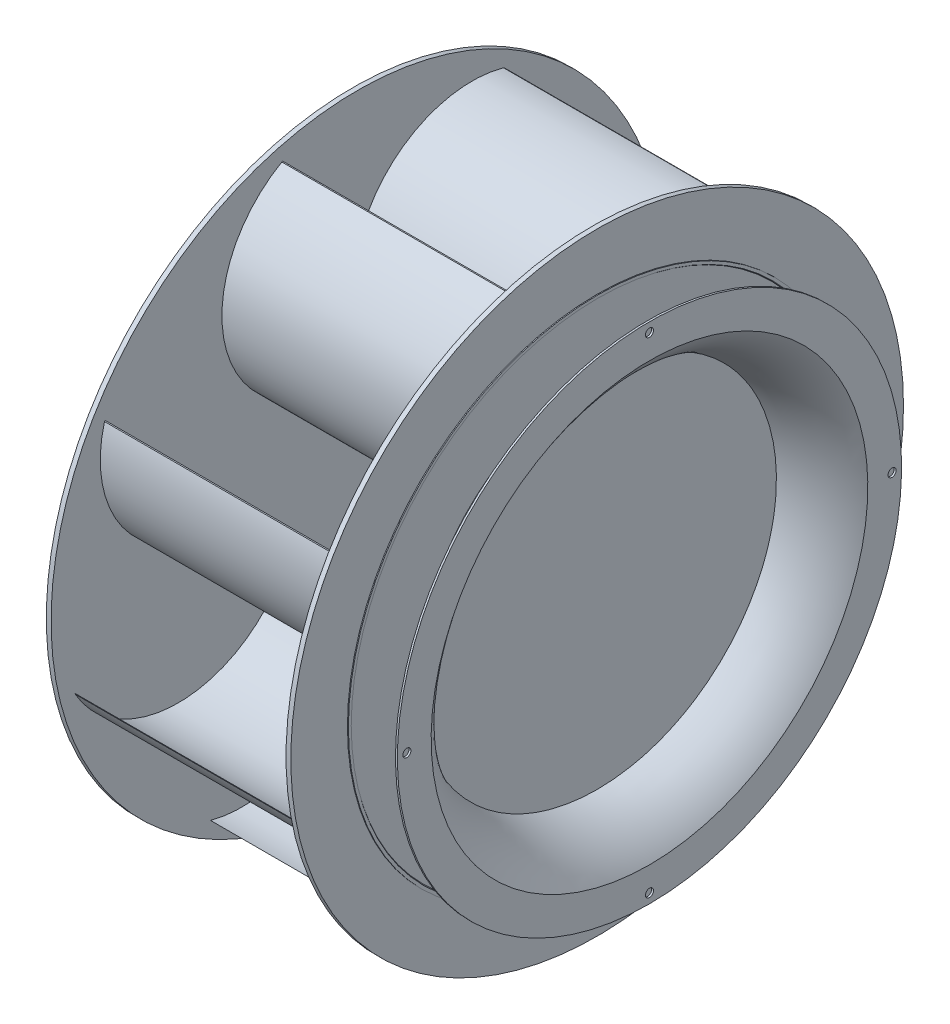
SolidWorks part; units mm, degrees
ref_plane "Front Plane" through (0, 0, 0) normal (0, 0, 1) x (1, 0, 0)
ref_plane "Top Plane" through (0, 0, 0) normal (0, 1, 0) x (1, 0, 0)
ref_plane "Right Plane" through (0, 0, 0) normal (1, 0, 0) x (0, 0, -1)
sketch "Sketch1" plane through (0, 0, 0) normal (0, 0, 1) x (1, 0, 0)
  line L0 (0, 0) -> (831.9083, 0) construction
  line L1 (0, 0) -> (0, 109)
  line L2 (5, 114) -> (70, 114)
  line L3 (70, 114) -> (70, 138)
  line L4 (70, 138) -> (90, 138)
  line L5 (90, 138) -> (90, 98)
  line L6 (90, 98) -> (95, 98)
  line L7 (95, 98) -> (95, 133)
  line L8 (95, 133) -> (105, 133)
  line L9 (105, 133) -> (105, 98)
  line L10 (105, 98) -> (129, 98)
  line L11 (129, 98) -> (129, 0)
  line L12 (129, 0) -> (0, 0)
  arc A0 (5, 114) -> (0, 109) centre (5, 109) ccw
  point P16 (0, 114)
  dimension "D10" = 5
  dimension "D1" = 114
  dimension "D2" = 24
  dimension "D3" = 70
  dimension "D4" = 40
  dimension "D5" = 35
  dimension "D6" = 5
  dimension "D7" = 20
  dimension "D8" = 10
  dimension "D9" = 59
revolve "Revolve1" add sketch "Sketch1" angle 360 about L0
sketch "Sketch2" plane through (129, 0, 0) normal (1, 0, 0) x (0, 0, -1)
  circle A0 centre (0, 0) radius 322
  dimension "D1" = 644
extrude "Extrude1" add sketch "Sketch2" along normal blind 5
sketch "Sketch9" plane through (129, 0, 0) normal (-1, 0, 0) x (0, 0, 1)
  circle A0 centre (0, 0) radius 317
  circle A1 centre (0, 0) radius 100
  circle A2 centre (0, 0) radius 322 construction
  dimension "D1" = 5
  dimension "D2" = 200
extrude "Extrude7" cut sketch "Sketch9" against normal blind 3
ref_plane "Plane1" through (381, 0, 0) normal (1, 0, 0) x (0, 0, -1)
sketch "Sketch3" plane through (381, 0, 0) normal (1, 0, 0) x (0, 0, -1)
  circle A0 centre (0, 0) radius 322
  dimension "D1" = 644
extrude "Extrude2" add sketch "Sketch3" along normal blind 5 separate body
sketch "Sketch4" plane through (134, 0, 0) normal (1, 0, 0) x (0, 0, -1)
  line L0 (0, 0) -> (0, 307) construction
  line L1 (0, 0) -> (161, 278.8602) construction
  line L2 (0, 112.5) -> (0.866, 112)
  line L3 (153.5, 265.8698) -> (154.366, 265.3698)
  circle A0 centre (0, 0) radius 307 construction
  circle A1 centre (0, 0) radius 322 construction
  circle A2 centre (0, 0) radius 112.5 construction
  arc A3 (0, 112.5) -> (153.5, 265.8698) centre (120.6282, 145.2694) cw
  arc A4 (0.866, 112) -> (154.366, 265.3698) centre (121.4942, 144.7694) cw
  dimension "D1" = 15
  dimension "D2" = 225
  dimension "D6" = 125
  dimension "D7" = 125
  dimension "D3" = 30
  dimension "D4" = 60
  dimension "D5" = 1
extrude "Extrude3" add sketch "Sketch4" along normal up to surface (252 mm away) up to face at (386, 0, -322)
ref_axis "Axis1" through (253.5503, 0, 0) along (-1, 0, 0)
pattern_circular "CirPattern1" count 8 over 360 about axis through (253.5503, 0, 0) along (-1, 0, 0) of "Extrude3"
sketch "Sketch5" plane through (0, 0, 0) normal (0, 0, 1) x (1, 0, 0)
  line L0 (0, 0) -> (527.2916, 0) construction
  line L1 (253.5503, 0) -> (75.411, 0) construction
  line L2 (386, 262.5) -> (387, 262.5)
  line L3 (387, 262.5) -> (387, 259.5)
  line L4 (386, 262.5) -> (386, 259.5)
  line L5 (360, 182.5) -> (360, 181.5)
  line L6 (70, 138) -> (70, -138) construction
  line L7 (386, -322) -> (386, 322) construction
  arc A0 (387, 259.5) -> (360, 182.5) centre (427.1772, 202.1781) ccw
  arc A1 (386, 259.5) -> (360, 181.5) centre (426.7494, 202.5835) ccw
  dimension "D7" = 70
  dimension "D8" = 70
  dimension "D1" = 181.5
  dimension "D2" = 1
  dimension "D3" = 1
  dimension "D4" = 3
  dimension "D5" = 262.5
  dimension "D6" = 290
revolve "Revolve2" add sketch "Sketch5" angle 360 about L0
ref_plane "Plane3" through (441, 0, 0) normal (1, 0, 0) x (0, 0, -1)
sketch "Sketch6" plane through (0, 0, 0) normal (0, 0, 1) x (1, 0, 0)
  line L0 (441, 265) -> (439, 265)
  line L1 (441, -251.35) -> (441, 251.35) construction
  line L2 (439, 265) -> (439, 229.5)
  line L3 (0, 0) -> (615.1417, 0) construction
  line L4 (0, 114) -> (0, -114) construction
  line L5 (253.5503, 0) -> (75.411, 0) construction
  line L6 (441, 265) -> (441, 229.5)
  line L7 (337, 187.5) -> (341, 187.5)
  line L8 (337, 187.5) -> (337, 185.5)
  line L9 (337, 185.5) -> (341, 185.5)
  arc A0 (341, 187.5) -> (439, 229.5) centre (356.6725, 286.2642) ccw
  arc A1 (341, 185.5) -> (441, 229.5) centre (357.266, 284.1682) ccw
  dimension "D7" = 100
  dimension "D8" = 100
  dimension "D1" = 265
  dimension "D2" = 2
  dimension "D3" = 229.5
  dimension "D4" = 104
  dimension "D5" = 187.5
  dimension "D6" = 4
revolve "Revolve3" add sketch "Sketch6" angle 360 about L3
sketch "Sketch7" plane through (441, 0, 0) normal (1, 0, 0) x (0, 0, -1)
  line L0 (0, 0) -> (0, 255) construction
  circle A0 centre (0, 0) radius 255 construction
  circle A1 centre (0, 255) radius 4.25
  dimension "D1" = 510
  dimension "D2" = 8.5
extrude "Extrude5" cut sketch "Sketch7" against normal blind 5
pattern_circular "CirPattern2" count 4 over 360 about axis through (253.5503, 0, 0) along (-1, 0, 0) of "Extrude5"
sketch "Sketch8" plane through (0, 0, 0) normal (1, 0, 0) x (0, 0, -1)
  line L0 (0, 0) -> (0, 126) construction
  circle A0 centre (0, 0) radius 126 construction
  circle A1 centre (0, 126) radius 5
  dimension "D1" = 252
  dimension "D2" = 10
extrude "Extrude6" cut sketch "Sketch8" along normal up to surface (90 mm away) up to face at (90, 0, 138)
pattern_circular "CirPattern3" count 8 over 360 about axis through (253.5503, 0, 0) along (-1, 0, 0) of "Extrude6"
